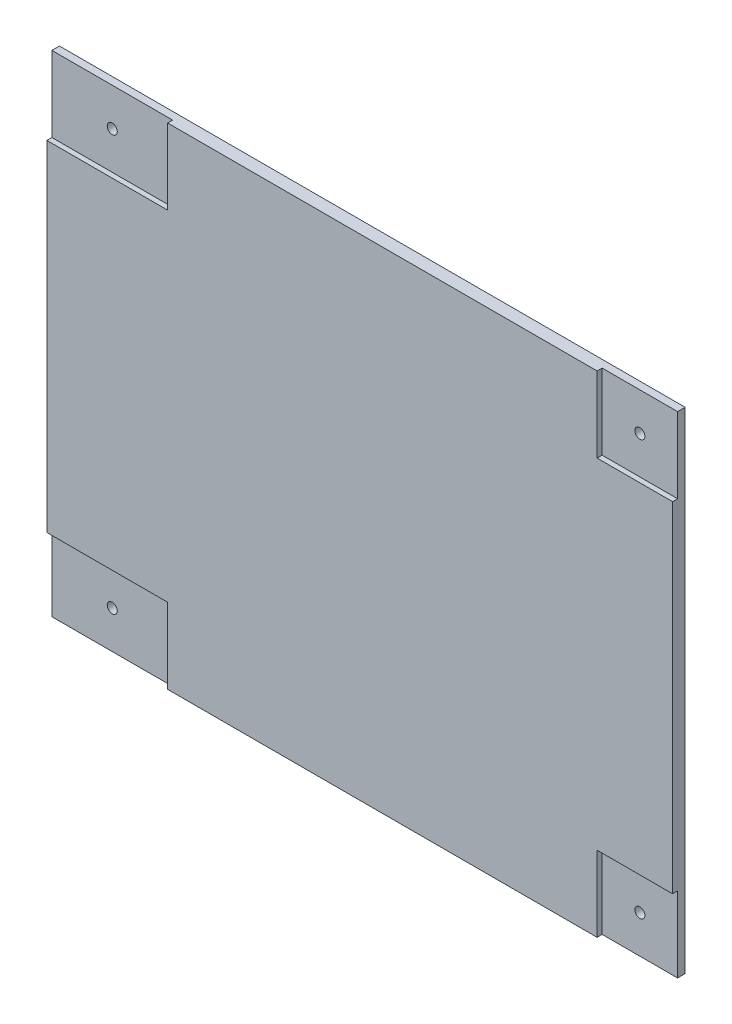
SolidWorks part; units mm, degrees
ref_plane "Alzado" through (0, 0, 0) normal (0, 0, 1) x (1, 0, 0)
ref_plane "Planta" through (0, 0, 0) normal (0, 1, 0) x (1, 0, 0)
ref_plane "Vista lateral" through (0, 0, 0) normal (1, 0, 0) x (0, 0, -1)
sketch "Croquis1" plane through (0, 0, 0) normal (0, 0, 1) x (1, 0, 0)
  line L1 (-117.2917, 97.7627) -> (131.4683, 97.7627)
  line L2 (-117.2917, 97.7627) -> (-117.2917, -97.2373)
  line L3 (-117.2917, -97.2373) -> (131.4683, -97.2373)
  line L4 (131.4683, 97.7627) -> (131.4683, -97.2373)
  dimension "D1" = 248.76
  dimension "D2" = 195
extrude "Saliente-Extruir1" add sketch "Croquis1" along normal blind 5
sketch "Croquis2" plane through (0, 0, 5) normal (0, 0, 1) x (1, 0, 0)
  line L0 (-117.2917, 0.2627) -> (131.4683, 0.2627) construction
  line L1 (-117.2917, 97.7627) -> (-117.2917, -97.2373) construction
  line L2 (131.4683, -97.2373) -> (131.4683, 97.7627) construction
  line L3 (-117.2917, -97.2373) -> (-69.2917, -97.2373)
  line L4 (-117.2917, -97.2373) -> (131.4683, -97.2373) construction
  line L5 (-69.2917, -97.2373) -> (-69.2917, -67.2373)
  line L6 (-69.2917, -67.2373) -> (-117.2917, -67.2373)
  line L7 (-117.2917, -67.2373) -> (-117.2917, -97.2373)
  line L8 (131.4683, 67.7627) -> (101.4683, 67.7627)
  line L9 (131.4683, -97.2373) -> (101.4683, -97.2373)
  line L10 (131.4683, -97.2373) -> (131.4683, -67.2373)
  line L11 (131.4683, -67.2373) -> (101.4683, -67.2373)
  line L12 (101.4683, -97.2373) -> (101.4683, -67.2373)
  line L13 (101.4683, 97.7627) -> (101.4683, 67.7627)
  line L14 (131.4683, 97.7627) -> (101.4683, 97.7627)
  line L15 (131.4683, 97.7627) -> (131.4683, 67.7627)
  line L16 (-69.2917, 67.7627) -> (-117.2917, 67.7627)
  line L17 (-69.2917, 97.7627) -> (-69.2917, 67.7627)
  line L18 (-117.2917, 97.7627) -> (-69.2917, 97.7627)
  line L19 (-117.2917, 67.7627) -> (-117.2917, 97.7627)
  dimension "D1" = 48
  dimension "D2" = 30
  dimension "D3" = 30
  dimension "D4" = 30
extrude "Cortar-Extruir1" cut sketch "Croquis2" against normal blind 2
sketch "Croquis3" plane through (0, 0, 5) normal (0, 0, 1) x (1, 0, 0)
  line L0 (-69.2917, 97.7627) -> (-117.2917, 97.7627) construction
  circle A0 centre (-93.2917, 82.7627) radius 2
  circle A1 centre (-93.2917, -82.2373) radius 2
  circle A2 centre (116.4683, 82.7627) radius 2
  circle A3 centre (116.4683, -82.2373) radius 2
  dimension "D2" = 4
  dimension "D3" = 4
  dimension "D5" = 4
  dimension "D6" = 4
  dimension "D1" = 15
  dimension "D4" = 15
  dimension "D7" = 209.76
  dimension "D8" = 165
extrude "Cortar-Extruir2" cut sketch "Croquis3" against normal blind 10
sketch "Croquis4" plane through (0, 0, 0) normal (0, 0, -1) x (-1, 0, 0)
  line L5 (-131.4683, -97.2373) -> (-131.4683, 97.7627) construction
  line L7 (-131.4683, 97.7627) -> (117.2917, 97.7627) construction
  circle A0 centre (-51.8719, 0.2627) radius 26.0452
  point P5 (0, 0)
  dimension "D1" = 79.5964
  dimension "D2" = 97.5
